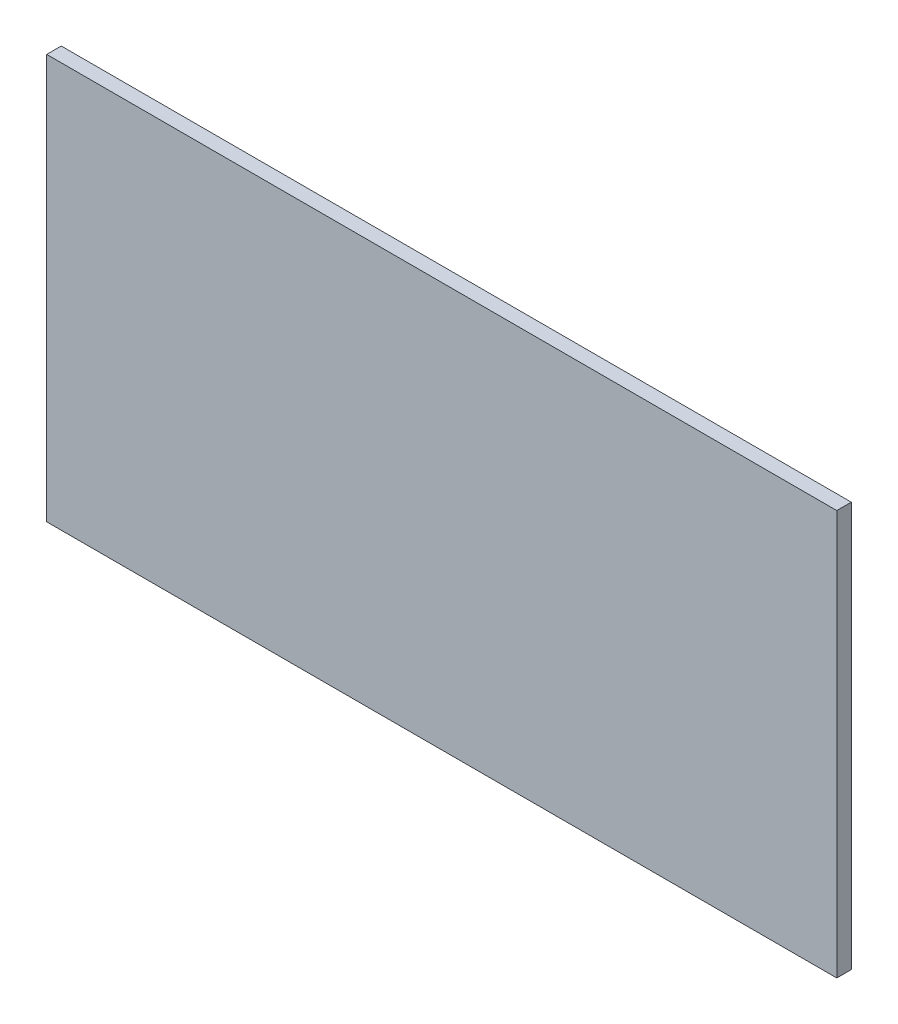
SolidWorks part; units mm, degrees
material "Thornel Mat VMA"
ref_plane "Front Plane" through (0, 0, 0) normal (0, 0, 1) x (1, 0, 0)
ref_plane "Top Plane" through (0, 0, 0) normal (0, 1, 0) x (1, 0, 0)
ref_plane "Right Plane" through (0, 0, 0) normal (1, 0, 0) x (0, 0, -1)
sketch "Sketch1" plane through (0, 0, 0) normal (0, 0, 1) x (1, 0, 0)
  line L1 (-20.4587, 47.6) -> (-183.6375, 47.6)
  line L2 (-20.4587, 47.6) -> (-20.4587, -36.0143)
  line L3 (-20.4587, -36.0143) -> (-183.6375, -36.0143)
  line L4 (-183.6375, 47.6) -> (-183.6375, -36.0143)
extrude "Boss-Extrude1" add sketch "Sketch1" along normal blind 3
